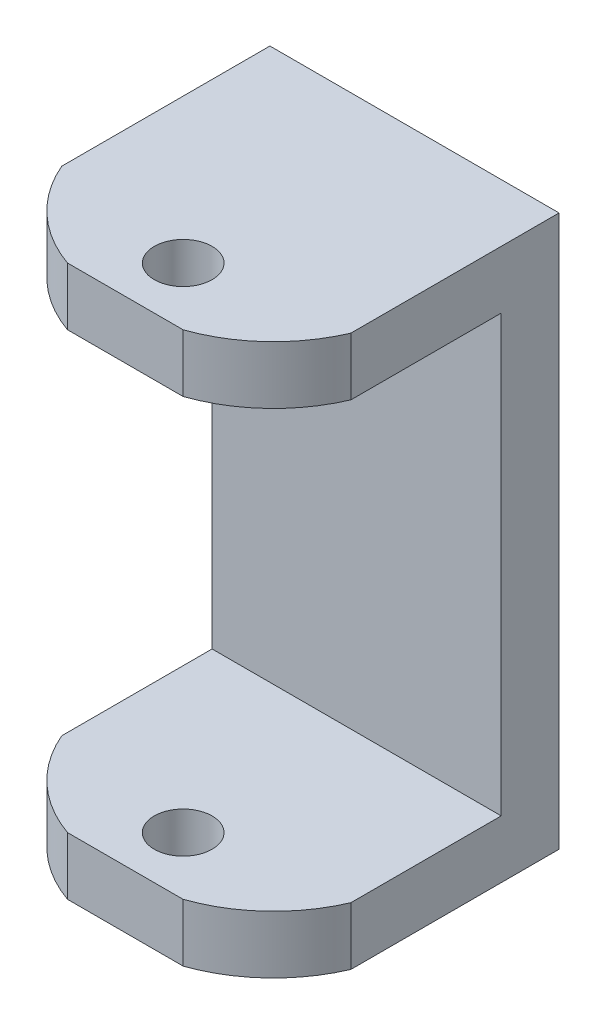
SolidWorks part; units mm, degrees
ref_plane "Front Plane" through (0, 0, 0) normal (0, 0, 1) x (1, 0, 0)
ref_plane "Top Plane" through (0, 0, 0) normal (0, 1, 0) x (1, 0, 0)
ref_plane "Right Plane" through (0, 0, 0) normal (1, 0, 0) x (0, 0, -1)
sketch "Sketch1" plane through (0, 0, 0) normal (0, 1, 0) x (1, 0, 0)
  line L1 (-5, 0) -> (5, 0)
  line L2 (-12.5, 7) -> (-12.5, 25)
  line L3 (-12.5, 25) -> (12.5, 25)
  line L4 (12.5, 7) -> (12.5, 25)
  arc A0 (5, 0) -> (12.5, 7) centre (0.8167, 12) ccw
  arc A1 (-5, 0) -> (-12.5, 7) centre (-0.8167, 12) cw
  circle A3 centre (0, 5) radius 2.5
  point P5 (0, 0)
  point P6 (0, 0)
  point P12 (-12.5, 0)
  point P13 (0, 25)
  point P14 (0, 0)
  point P16 (0, 0)
  dimension "D3" = 10
  dimension "D4" = 20
  dimension "D6" = 5
  dimension "D1" = 25
  dimension "D2" = 25
  dimension "D5" = 13
  dimension "D7" = 7
extrude "Boss-Extrude1" add sketch "Sketch1" along normal blind 47.65
sketch "Sketch2" plane through (-12.5, 0, 0) normal (-1, 0, 0) x (0, 0, 1)
  line L0 (0, 47.65) -> (0, 0) construction
  line L1 (0, 5) -> (-20, 5)
  line L2 (0, 5) -> (0, 42.65)
  line L3 (0, 42.65) -> (-20, 42.65)
  line L4 (-20, 5) -> (-20, 42.65)
  point P6 (0, 23.825)
  point P7 (0, 23.825)
  dimension "D1" = 37.65
  dimension "D2" = 20
extrude "Cut-Extrude1" cut sketch "Sketch2" against normal through all
ref_plane "B mid plane" through (0, 23.825, 0) normal (0, -1, 0) x (-1, 0, 0)
